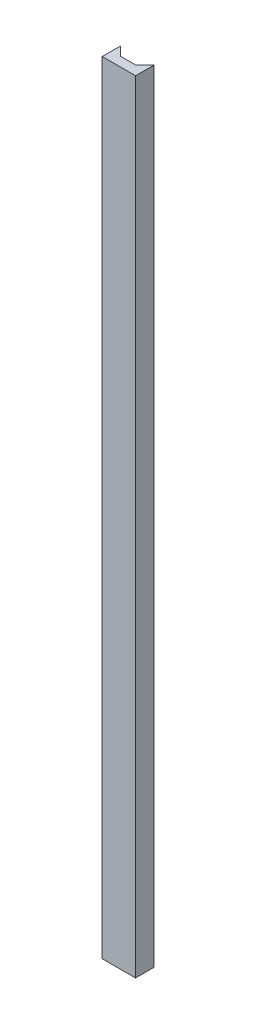
SolidWorks part; units mm, degrees
ref_plane "Front Plane" through (0, 0, 0) normal (0, 0, 1) x (1, 0, 0)
ref_plane "Top Plane" through (0, 0, 0) normal (0, 1, 0) x (1, 0, 0)
ref_plane "Right Plane" through (0, 0, 0) normal (1, 0, 0) x (0, 0, -1)
sketch "Sketch2" plane through (0, 0, 0) normal (0, 0, 1) x (1, 0, 0)
  line L1 (0, 0) -> (-5, 0)
  line L2 (0, 0) -> (0, -250)
  line L3 (0, -250) -> (-5, -250)
  line L4 (-5, 0) -> (-5, -250)
  dimension "D1" = 5
  dimension "D2" = 250
extrude "Boss-Extrude1" add sketch "Sketch2" along normal blind 3
sketch "Sketch4" plane through (0, -250, 0) normal (0, -1, 0) x (-1, 0, 0)
  line L0 (0, 0) -> (-2.8284, 2.8284)
  line L1 (-2.8284, 2.8284) -> (-2.8284, -3)
  line L2 (-2.8284, -3) -> (0, -3)
  line L3 (0, -3) -> (0, 0)
  line L4 (2.5, 0) -> (2.5, -3.7119) construction
  line L5 (5, 0) -> (0, 0) construction
  line L6 (7.8284, -3) -> (5, -3)
  line L7 (7.8284, 2.8284) -> (7.8284, -3)
  line L8 (5, 0) -> (7.8284, 2.8284)
  line L9 (5, -3) -> (5, 0)
  dimension "D1" = 135
  dimension "D2" = 4
extrude "Boss-Extrude2" add sketch "Sketch4" against normal up to vertex (250 mm away) up to point (0, 0, 0)
